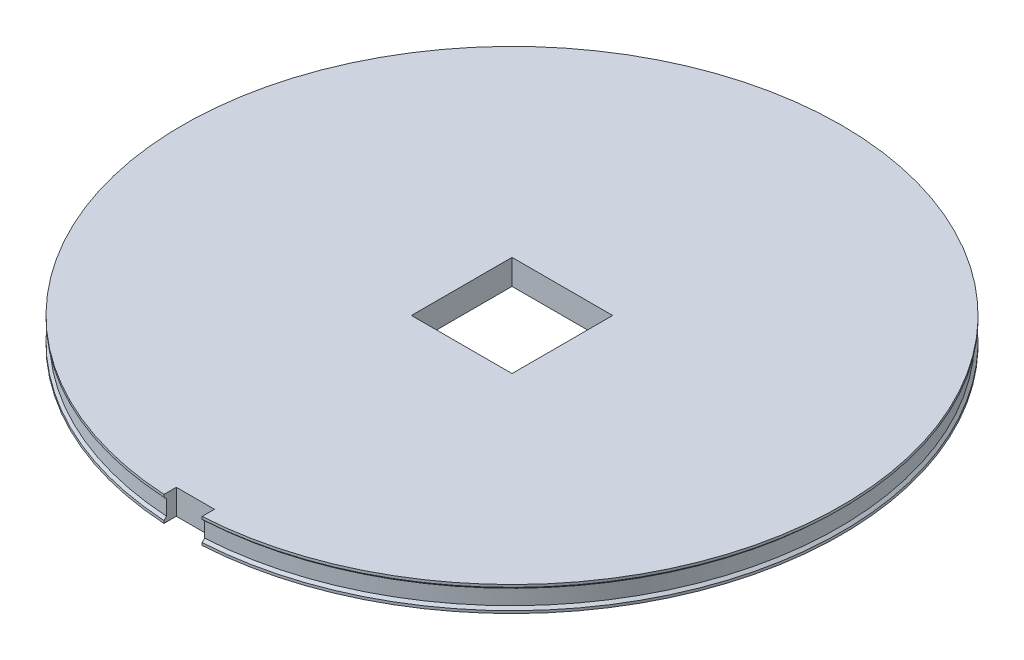
SolidWorks part; units mm, degrees
ref_plane "Front" through (0, 0, 0) normal (0, 0, 1) x (1, 0, 0)
ref_plane "Top" through (0, 0, 0) normal (0, 1, 0) x (1, 0, 0)
ref_plane "Right" through (0, 0, 0) normal (1, 0, 0) x (0, 0, -1)
sketch "Skizze1" plane through (0, 0, 0) normal (0, 1, 0) x (1, 0, 0)
  line L1 (-20, -20) -> (20, -20)
  line L2 (-20, -20) -> (-20, 20)
  line L3 (-20, 20) -> (20, 20)
  line L4 (20, -20) -> (20, 20)
  line L5 (-20, -20) -> (20, 20) construction
  line L6 (-20, 20) -> (20, -20) construction
  circle A0 centre (0, 0) radius 131
  dimension "D1" = 262
  dimension "D2" = 40
extrude "Aufsatz-Linear austragen1" add sketch "Skizze1" along normal blind 10
sketch "Skizze2" plane through (0, 0, 0) normal (0, 1, 0) x (1, 0, 0)
  line L0 (0, 0) -> (0, -155.4222) construction
  line L1 (-7.5807, -125.8678) -> (7.5807, -125.8678)
  line L2 (7.5807, -125.8678) -> (7.5807, -133.3827)
  line L3 (7.5807, -133.3827) -> (-7.5807, -133.3827)
  line L4 (-7.5807, -125.8678) -> (-7.5807, -133.3827)
  point P8 (0, -133.3827)
  point P9 (0, -125.8678)
extrude "Schnitt-Linear austragen1" cut sketch "Skizze2" along normal through all
sketch "Skizze4" plane through (0, 0, 0) normal (1, 0, 0) x (0, 0, -1)
  line L0 (131, 10) -> (131, 0) construction
  line L1 (-130.7805, 0) -> (131, 0) construction
  line L2 (0, 0) -> (0, 11.8712) construction
  line L4 (131, 5) -> (122.2036, 5) construction
  line L5 (131, 8) -> (130, 8)
  line L6 (130, 8) -> (130, 2)
  line L7 (131, 2) -> (130, 2)
  line L8 (131, 8) -> (133.6119, 8)
  line L9 (133.6119, 8) -> (133.6119, 2)
  line L10 (133.6119, 2) -> (131, 2)
  point P17 (130, 5)
  dimension "D1" = 2
  dimension "D2" = 6
revolve "Schnitt-Rotation2" cut sketch "Skizze4" angle 360 about L2
chamfer "Fase1" distance 1 angle 45 2 edges at (0, 8, -131) (0, 2, -131)
